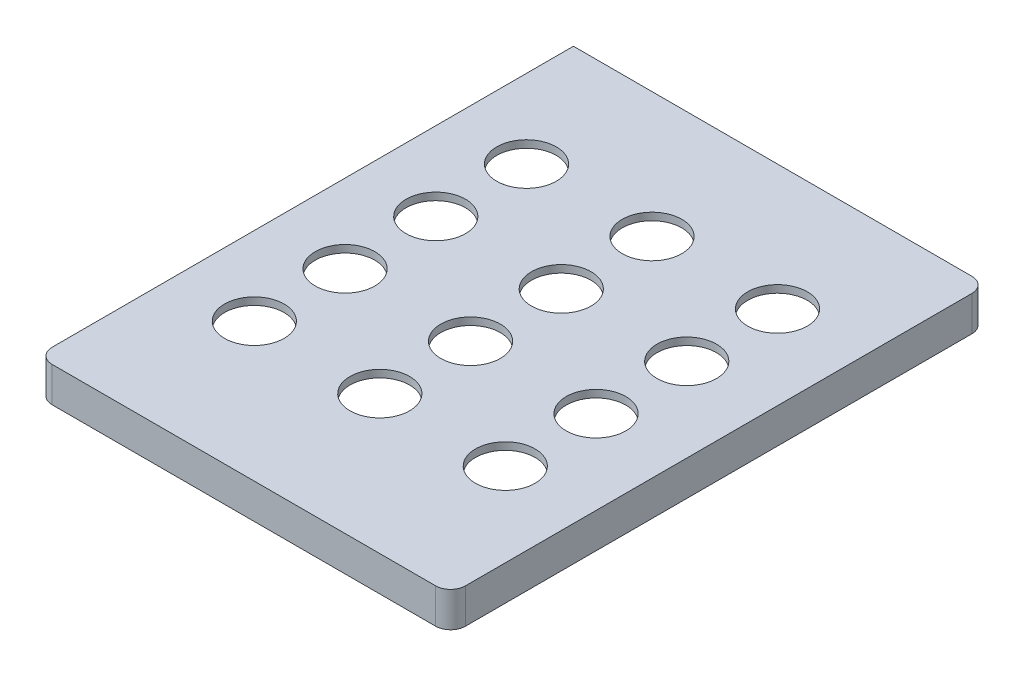
SolidWorks part; units mm, degrees
ref_plane "Front Plane" through (0, 0, 0) normal (0, 0, 1) x (1, 0, 0)
ref_plane "Top Plane" through (0, 0, 0) normal (0, 1, 0) x (1, 0, 0)
ref_plane "Right Plane" through (0, 0, 0) normal (1, 0, 0) x (0, 0, -1)
sketch "Sketch2" plane through (0, 12.5, 0) normal (0, 1, 0) x (1, 0, 0)
  line L0 (0, 0) -> (0, 25.4065) construction
  line L1 (-26.5, 30.5) -> (26.5, 30.5)
  line L2 (-26.5, 30.5) -> (-26.5, -30.5)
  line L3 (-26.5, -30.5) -> (26.5, -30.5)
  line L4 (26.5, 30.5) -> (26.5, -30.5)
  line L5 (-26.5, 30.5) -> (26.5, -30.5) construction
  line L6 (-26.5, -30.5) -> (26.5, 30.5) construction
  line L8 (27.75, 36) -> (-27.75, 36) construction
  point P0 (0, 0)
  dimension "D1" = 53
  dimension "D2" = 61
  dimension "D3" = 5.5
extrude "Cut-Extrude1" cut sketch "Sketch2" against normal blind 1.65 rebuild error yes
sketch "Sketch3" plane through (0, 12.5, 0) normal (0, 1, 0) x (1, 0, 0)
  line L0 (0, 0) -> (0, 22.2703) construction
  line L1 (22, 29) -> (-22, 29)
  line L2 (22, 29) -> (22, -34.5)
  line L3 (22, -34.5) -> (-22, -34.5)
  line L4 (-22, 29) -> (-22, -34.5)
  line L5 (22, 29) -> (-22, -34.5) construction
  line L6 (22, -34.5) -> (-22, 29) construction
  line L7 (-27.75, -36) -> (27.75, -36) construction
  point P0 (0, -2.75)
  dimension "D1" = 63.5
  dimension "D2" = 44
  dimension "D3" = 1.5
extrude "Cut-Extrude2" cut sketch "Sketch3" against normal blind 11.5 rebuild error yes
sketch "Sketch4" plane through (0, 12.5, 0) normal (0, 1, 0) x (1, 0, 0)
  line L1 (22, -34.5) -> (-22, -34.5)
  line L2 (22, -34.5) -> (22, -30.5)
  line L3 (22, -30.5) -> (-22, -30.5)
  line L4 (-22, -34.5) -> (-22, -30.5)
sketch "Sketch5" plane through (0, 10.85, 0) normal (0, 1, 0) x (1, 0, 0)
  line L0 (-22, 29) -> (-22, -30.5) construction
  line L1 (22, -30.5) -> (-22, -30.5)
  line L2 (22, -30.5) -> (22, -27)
  line L3 (22, -27) -> (-22, -27)
  line L4 (-22, -30.5) -> (-22, -27)
  dimension "D1" = 3.5
sketch "Sketch6" plane through (0, 10.85, 0) normal (0, 1, 0) x (1, 0, 0)
  line L0 (22, 29) -> (-22, 29) construction
  line L1 (22, -27) -> (23.5, -27)
  line L2 (22, -27) -> (22, 29)
  line L3 (22, 29) -> (23.5, 29)
  line L4 (23.5, -27) -> (23.5, 29)
  line L5 (26.5, -30.5) -> (26.5, 30.5) construction
  line L6 (-26.5, 30.5) -> (-26.5, -30.5) construction
  line L7 (-22, -27) -> (-23.5, -27)
  line L8 (-22, -27) -> (-22, 29)
  line L9 (-22, 29) -> (-23.5, 29)
  line L10 (-23.5, -27) -> (-23.5, 29)
  dimension "D1" = 3
  dimension "D2" = 3
extrude "Cut-Extrude3" cut sketch "Sketch6" against normal blind 3 rebuild error yes
sketch "Sketch7" plane through (0, 12.5, 0) normal (0, 1, 0) x (1, 0, 0)
  line L0 (-27.75, 36) -> (-27.75, -36) construction
  line L1 (-27.75, 27.25) -> (-20.75, 27.25)
  line L2 (-27.75, 27.25) -> (-27.75, 18.75)
  line L3 (-27.75, 18.75) -> (-20.75, 18.75)
  line L4 (-20.75, 27.25) -> (-20.75, 18.75)
  line L5 (26.5, 30.5) -> (-26.5, 30.5) construction
  dimension "D1" = 8.5
  dimension "D2" = 3.25
  dimension "D3" = 7
extrude "Cut-Extrude4" cut sketch "Sketch7" against normal blind 4.5 rebuild error yes
sketch "Sketch8" plane through (0, 12.5, 0) normal (0, 1, 0) x (1, 0, 0)
  line L0 (26.5, -30.5) -> (26.5, 30.5) construction
  line L1 (24.5, 28) -> (-11.5, 28)
  line L2 (24.5, 28) -> (24.5, 35)
  line L3 (24.5, 35) -> (-11.5, 35)
  line L4 (-11.5, 28) -> (-11.5, 35)
  line L5 (27.75, 36) -> (-27.75, 36) construction
  line L6 (26.5, 30.5) -> (-26.5, 30.5) construction
  dimension "D1" = 2
  dimension "D2" = 38
  dimension "D3" = 1
  dimension "D4" = 2.5
extrude "Cut-Extrude5" cut sketch "Sketch8" against normal blind 7.6 rebuild error yes
sketch "Sketch9" plane through (0, 0, -36) normal (0, 0, -1) x (-1, 0, 0)
  line L1 (-27.75, 0) -> (11.5, 0)
  line L2 (-27.75, 0) -> (-27.75, 3.9)
  line L3 (-27.75, 3.9) -> (11.5, 3.9)
  line L4 (11.5, 0) -> (11.5, 3.9)
  line L5 (27.75, 12.5) -> (27.75, 0) construction
  dimension "D1" = 3.9
  dimension "D2" = 16.25
extrude "Cut-Extrude6" cut sketch "Sketch9" against normal blind 6 rebuild error yes
fillet "Fillet3" radius 1 rebuild error yes
sketch "Sketch10" plane through (0, 12.5, 0) normal (0, 1, 0) x (1, 0, 0)
  line L0 (27.75, -34) -> (27.75, 34) construction
  line L1 (-25.75, -36) -> (25.75, -36) construction
  circle A0 centre (24.95, -33.2) radius 1
  dimension "D1" = 2
  dimension "D2" = 2.8
  dimension "D3" = 2.8
extrude "Cut-Extrude7" cut sketch "Sketch10" against normal through all rebuild error yes
sketch "Sketch11" plane through (0, 12.5, 0) normal (0, 1, 0) x (1, 0, 0)
  line L0 (25.75, 36) -> (-27.75, 36) construction
  line L1 (-27.75, 36) -> (-27.75, 27.25) construction
  line L2 (-27.75, 27.25) -> (-27.75, 18.75) construction
  line L3 (25.75, 36) -> (-27.75, 36)
  line L4 (-27.75, 36) -> (-27.75, 27.25)
  line L5 (-27.75, 27.25) -> (-27.75, 18.75)
  line L6 (-27.75, 18.75) -> (-27.75, -34) construction
  line L7 (-27.75, 18.75) -> (-27.75, -34)
  line L8 (27.75, -34) -> (27.75, 34) construction
  line L9 (27.75, -34) -> (27.75, 34)
  line L10 (-25.75, -36) -> (25.75, -36) construction
  line L11 (-25.75, -36) -> (25.75, -36)
  line L12 (-26.5, 18.75) -> (-26.5, -30.5) construction
  line L13 (-26.5, 34) -> (-26.5, -30.5)
  line L15 (25.45, 34) -> (25.45, -30.5)
  line L16 (-26.5, 34) -> (25.45, 34)
  line L18 (25.45, -30.5) -> (-26.5, -30.5)
  arc A0 (27.75, 34) -> (25.75, 36) centre (25.75, 34) ccw construction
  arc A1 (27.75, 34) -> (25.75, 36) centre (25.75, 34) ccw
  arc A2 (25.75, -36) -> (27.75, -34) centre (25.75, -34) ccw construction
  arc A3 (-27.75, -34) -> (-25.75, -36) centre (-25.75, -34) ccw construction
  arc A4 (25.75, -36) -> (27.75, -34) centre (25.75, -34) ccw
  arc A5 (-27.75, -34) -> (-25.75, -36) centre (-25.75, -34) ccw
  dimension "D1" = 2.3
extrude "Boss-Extrude4" add sketch "Sketch11" along normal blind 3.7 separate body
sketch "Sketch12" plane through (0, 16.2, 0) normal (0, 1, 0) x (1, 0, 0)
  line L0 (-25.75, -36) -> (25.75, -36) construction
  line L1 (-25.75, -36) -> (25.75, -36)
  line L2 (-27.75, 36) -> (-27.75, -34) construction
  line L3 (-27.75, 36) -> (-27.75, -34)
  line L4 (27.75, -34) -> (27.75, 34) construction
  line L5 (27.75, -34) -> (27.75, 34)
  line L6 (25.75, 36) -> (-27.75, 36) construction
  line L7 (25.75, 36) -> (-27.75, 36)
  line L8 (-17.2, -17.4) -> (-0.35, -17.4) construction
  line L9 (16.5, -17.4) -> (16.5, 19.15) construction
  line L10 (16.5, 19.15) -> (-17.2, 19.15) construction
  line L11 (-17.2, 19.15) -> (-17.2, -17.4) construction
  line L12 (-17.2, 6.9667) -> (16.5, 6.9667) construction
  line L13 (16.5, -5.2167) -> (-17.2, -5.2167) construction
  line L14 (-0.35, -17.4) -> (-0.35, -5.2167) construction
  line L15 (-0.35, -5.2167) -> (-0.35, 6.9667) construction
  line L16 (-0.35, 6.9667) -> (-0.35, 19.15) construction
  line L17 (-0.35, -17.4) -> (16.5, -17.4) construction
  arc A0 (25.75, -36) -> (27.75, -34) centre (25.75, -34) ccw construction
  arc A1 (25.75, -36) -> (27.75, -34) centre (25.75, -34) ccw
  arc A2 (-27.75, -34) -> (-25.75, -36) centre (-25.75, -34) ccw construction
  arc A3 (-27.75, -34) -> (-25.75, -36) centre (-25.75, -34) ccw
  arc A4 (27.75, 34) -> (25.75, 36) centre (25.75, 34) ccw construction
  arc A5 (27.75, 34) -> (25.75, 36) centre (25.75, 34) ccw
  circle A6 centre (-17.2, -17.4) radius 4
  circle A7 centre (-17.2, -5.2167) radius 4
  circle A8 centre (-17.2, 6.9667) radius 4
  circle A9 centre (-17.2, 19.15) radius 4
  circle A10 centre (-0.35, 19.15) radius 4
  circle A11 centre (-0.35, 6.9667) radius 4
  circle A12 centre (-0.35, -5.2167) radius 4
  circle A13 centre (-0.35, -17.4) radius 4
  circle A14 centre (16.5, -17.4) radius 4
  circle A15 centre (16.5, -5.2167) radius 4
  circle A16 centre (16.5, 6.9667) radius 4
  circle A17 centre (16.5, 19.15) radius 4
  dimension "D2" = 8
  dimension "D1" = 18.6
  dimension "D3" = 10.55
  dimension "D4" = 16.85
  dimension "D5" = 11.25
extrude "Boss-Extrude5" add sketch "Sketch12" along normal blind 1
